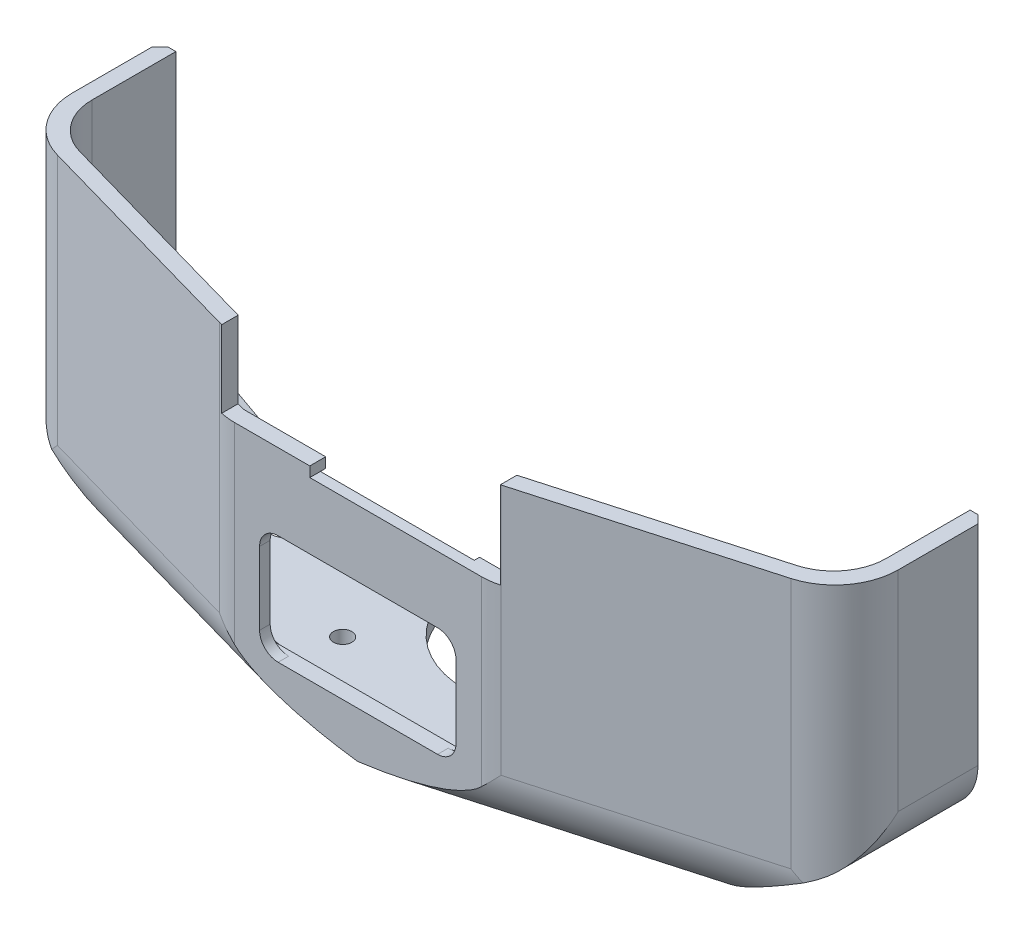
SolidWorks part; units mm, degrees
material "ABS"
ref_plane "Front Plane" through (0, 0, 0) normal (0, 0, 1) x (1, 0, 0)
ref_plane "Top Plane" through (0, 0, 0) normal (0, 1, 0) x (1, 0, 0)
ref_plane "Right Plane" through (0, 0, 0) normal (1, 0, 0) x (0, 0, -1)
sketch "Sketch1" plane through (0, 0, 0) normal (0, 0, 1) x (1, 0, 0)
  line L0 (-78, -21.6306) -> (78, -21.6306) construction
  line L1 (-52, -41.6306) -> (52, -41.6306)
  line L2 (-78, -27.6306) -> (-78, 17.8694)
  line L3 (-78, 17.8694) -> (78, 17.8694)
  line L4 (78, -27.6306) -> (78, 17.8694)
  line L5 (-78, -27.6306) -> (-52, -41.6306)
  line L7 (78, -27.6306) -> (52, -41.6306)
  line L8 (0, -21.6306) -> (0, 0) construction
  line L9 (0, -41.6306) -> (0, -21.6306) construction
  dimension "D1" = 39.5
  dimension "D2" = 156
  dimension "D3" = 14
  dimension "D5" = 104
  dimension "D6" = 20
extrude "Boss-Extrude1" add sketch "Sketch1" along normal blind 30 and the other way blind 10.64
sketch "Sketch2" plane through (0, 17.8694, 0) normal (0, 1, 0) x (1, 0, 0)
  line L0 (-78, -15) -> (-25, -30)
  line L1 (-78, -30) -> (-78, 10.64) construction
  line L2 (78, -30) -> (-78, -30) construction
  line L3 (-25, -30) -> (25, -30)
  line L4 (25, -30) -> (78, -15)
  line L5 (78, -30) -> (78, 10.64) construction
  line L6 (78, -15) -> (78, -44.6495)
  line L7 (78, -44.6495) -> (-78, -44.6495)
  line L8 (-78, -44.6495) -> (-78, -15)
  dimension "D1" = 50
  dimension "D2" = 15
extrude "Cut-Extrude1" cut sketch "Sketch2" against normal through all
shell "Shell1" thickness 3
sketch "Sketch7" plane through (0, 14.8694, 0) normal (0, -1, 0) x (1, 0, 0)
  line L0 (-52, -10.64) -> (52, -10.64) construction
  line L3 (-24.34, 27.069) -> (24.34, 27.069)
  line L6 (75, -10.64) -> (-75, -10.64)
  line L10 (75, -10.64) -> (75, 5.1686)
  line L13 (24.34, 27.069) -> (67.7232, 14.7907)
  line L14 (-24.34, 27.069) -> (-67.7232, 14.7907)
  line L15 (-75, -10.64) -> (-75, 5.1686)
  line L16 (78, -10.64) -> (78, 15) construction
  line L17 (-78, -10.64) -> (-78, 15) construction
  line L19 (-25, 30) -> (-78, 15) construction
  line L20 (78, 15) -> (25, 30) construction
  line L21 (65, 5.1686) -> (-65, 5.1686) construction
  arc A0 (75, 5.1686) -> (67.7232, 14.7907) centre (65, 5.1686) ccw
  arc A1 (-67.7232, 14.7907) -> (-75, 5.1686) centre (-65, 5.1686) ccw
  dimension "D1" = 3
  dimension "D2" = 3
  dimension "D3" = 3
  dimension "D4" = 10
  dimension "D5" = 10
  dimension "D6" = 48.68
  dimension "D7" = 0.66
extrude "Cut-Extrude4" cut sketch "Sketch7" against normal blind 10 and the other way blind 4
fillet "Fillet1" radius 12 12 edges at (0, -41.6306, 30) (-65, -34.6306, 18.6792) (65, -34.6306, 18.6792) (-78, -4.8806, 15) (-38.5, -41.6306, 26.1792) (-25, -11.8806, 30) (38.5, -41.6306, 26.1792) (25, -11.8806, 30) (78, -4.8806, 15) (-37.9136, -38.6306, 23.2274) (37.9136, -38.6306, 23.2274) (0, -38.6306, 27)
sketch "Sketch4" plane through (0, -38.6306, 0) normal (0, 1, 0) x (1, 0, 0)
  line L0 (-42.696, -12.86) -> (63.1659, -12.86) construction
  line L1 (0, 63.5417) -> (0, -42.2617) construction
  line L4 (-51.2436, 10.64) -> (51.2436, 10.64) construction
  circle A0 centre (-20, -12.86) radius 1.75
  circle A1 centre (20, -12.86) radius 1.75
  point P12 (0, 10.64)
  dimension "D1" = 3.5
  dimension "D2" = 3.5
  dimension "D3" = 20
  dimension "D4" = 20
  dimension "D5" = 23.5
extrude "Cut-Extrude2" cut sketch "Sketch4" against normal blind 30
sketch "Sketch18" plane through (0, 14.8694, 0) normal (0, -1, 0) x (1, 0, 0)
  line L0 (75, 5.1686) -> (75, 12.7312) construction
  line L1 (75, 12.7312) -> (67.7232, 14.7907) construction
  line L2 (-67.7232, 14.7907) -> (-75, 12.7312) construction
  line L3 (-75, 12.7312) -> (-75, 5.1686) construction
  line L4 (75, 5.1686) -> (75, 12.7312)
  line L5 (75, 12.7312) -> (67.7232, 14.7907)
  line L6 (-67.7232, 14.7907) -> (-75, 12.7312)
  line L7 (-75, 12.7312) -> (-75, 5.1686)
  arc A0 (75, 5.1686) -> (67.7232, 14.7907) centre (65, 5.1686) ccw construction
  arc A1 (-67.7232, 14.7907) -> (-75, 5.1686) centre (-65, 5.1686) ccw construction
  arc A2 (75, 5.1686) -> (67.7232, 14.7907) centre (65, 5.1686) ccw
  arc A3 (-67.7232, 14.7907) -> (-75, 5.1686) centre (-65, 5.1686) ccw
extrude "Boss-Extrude2" add sketch "Sketch18" along normal up to next
fillet "Fillet2" radius 10 4 edges at (-78, -27.6306, -2.3576) (-52, -41.6306, -0.3764) (52, -41.6306, -0.3764) (78, -27.6306, -2.3576)
sketch "Sketch12" plane through (0, -41.6306, 0) normal (0, -1, 0) x (1, 0, 0)
  line L1 (17.1361, -11.1904) -> (-17.1361, -11.1904)
  line L3 (-49.4788, -10.64) -> (49.4788, -10.64) construction
  arc A0 (17.1361, -11.1904) -> (-17.1361, -11.1904) centre (0, -7.64) ccw
  dimension "D1" = 35
  dimension "D2" = 3
extrude "Cut-Extrude5" cut sketch "Sketch12" against normal up to surface (3 mm away) up to face at (-20, -38.6306, 14.61)
sketch "Sketch13" plane through (0, 0, 30) normal (0, 0, 1) x (1, 0, 0)
  line L0 (23.3346, 17.8694) -> (-23.3346, 17.8694) construction
  line L2 (26.5, 17.8694) -> (26.5, 1.4694)
  line L5 (0, -40.4493) -> (0, 17.8694) construction
  line L13 (-26, 17.8694) -> (-26, 3.3737)
  line L14 (26.5, 1.4694) -> (-9.07, 1.4694)
  line L15 (26.5, 17.8694) -> (0, 17.8694)
  line L16 (0, 17.8694) -> (-26, 17.8694)
  line L17 (-26, 3.3737) -> (-9.07, 3.3737)
  line L18 (-9.07, 17.8694) -> (-9.07, 1.4694) construction
  line L19 (-9.07, 3.3737) -> (-9.07, 1.4694)
  dimension "D1" = 26
  dimension "D2" = 16.4
  dimension "D7" = 26.5
extrude "Cut-Extrude6" cut sketch "Sketch13" against normal blind 10
sketch "Sketch16" plane through (0, 0, 30) normal (0, 0, 1) x (1, 0, 0)
  line L0 (-9.07, 1.4694) -> (23.3346, 1.4694) construction
  line L1 (18.55, -31.7306) -> (-18.55, -31.7306)
  line L2 (18.55, -31.7306) -> (18.55, -11.0306)
  line L3 (18.55, -11.0306) -> (-18.55, -11.0306)
  line L4 (-18.55, -31.7306) -> (-18.55, -11.0306)
  line L5 (0, 1.4694) -> (0, -31.7306) construction
  dimension "D1" = 12.5
  dimension "D2" = 20.7
  dimension "D3" = 37.1
extrude "Cut-Extrude8" cut sketch "Sketch16" against normal up to surface (3 mm away)
fillet "Fillet3" radius 3.48 4 edges at (-18.55, -11.0306, 28.5) (-18.55, -31.7306, 28.5) (18.55, -31.7306, 28.5) (18.55, -11.0306, 28.5)
sketch "Sketch17" plane through (0, -31.7306, 0) normal (0, 1, 0) x (1, 0, 0)
  line L1 (-9.07, -27) -> (24.5836, -27) construction
  line L2 (-20, -27) -> (20, -27)
  line L3 (-20, -27) -> (-20, -28)
  line L4 (-20, -28) -> (20, -28)
  line L5 (20, -27) -> (20, -28)
  line L6 (-9.07, -30) -> (23.3346, -30) construction
  point P9 (0, -27)
  dimension "D1" = 2
  dimension "D2" = 40
extrude "Cut-Extrude10" cut sketch "Sketch17" along normal up to surface (33.2 mm away) up to face at (13.7987, 1.4694, 28.3564)
sketch "Sketch19" plane through (0, 17.8694, 0) normal (0, 1, 0) x (1, 0, 0)
  line L1 (-75, 10.64) -> (-76.6, 10.64)
  line L2 (-75, 10.64) -> (-75, -3.86)
  line L3 (-75, -3.86) -> (-76.6, -3.86)
  line L4 (-76.6, 10.64) -> (-76.6, -3.86)
  line L5 (75, 10.64) -> (76.6, 10.64)
  line L6 (75, 10.64) -> (75, -3.86)
  line L7 (75, -3.86) -> (76.6, -3.86)
  line L8 (76.6, 10.64) -> (76.6, -3.86)
  dimension "D1" = 14.5
  dimension "D2" = 1.6
extrude "Cut-Extrude11" [suppressed] cut sketch "Sketch19" against normal blind 12
sketch "Sketch20" plane through (78, 0, 0) normal (1, 0, 0) x (0, 0, -1)
  line L0 (10.64, 17.8694) -> (-5.9249, 17.8694) construction
  line L1 (10.64, -21.6577) -> (10.64, 17.8694) construction
  circle A0 centre (1.64, 12.3694) radius 1.75
  dimension "D1" = 3.5
  dimension "D2" = 5.5
  dimension "D3" = 9
extrude "Cut-Extrude12" [suppressed] cut sketch "Sketch20" against normal through all
sketch "Sketch21" plane through (0, -38.6306, 0) normal (0, 1, 0) x (1, 0, 0)
  line L0 (-52.8475, 10.64) -> (-52.8475, -8.7796)
  line L1 (-75, 10.64) -> (-51.2436, 10.64) construction
  line L2 (-52.8475, -8.7796) -> (-33.4259, -22.2861)
  line L3 (-33.4259, -22.2861) -> (33.4259, -22.2861)
  line L4 (33.4259, -22.2861) -> (52.8475, -7.1244)
  line L5 (52.8475, -7.1244) -> (52.8475, 10.64)
  line L6 (51.2436, 10.64) -> (75, 10.64) construction
  line L7 (-52.8475, 10.64) -> (52.8475, 10.64)
  point P20 (0, 10.64)
  point P22 (0, -22.2861)
extrude "Cut-Extrude13" cut sketch "Sketch21" along normal blind 10
sketch "Sketch22" plane through (0, -41.6306, 0) normal (0, -1, 0) x (1, 0, 0)
  line L0 (-43.75, -0.64) -> (43.75, -0.64) construction
  line L1 (-49.4788, -10.64) -> (-17.2409, -10.64) construction
  line L2 (-47.25, -0.64) -> (-47.25, -10.64)
  line L3 (-47.25, -10.64) -> (-40.25, -10.64)
  line L4 (-40.25, -10.64) -> (-40.25, -0.64)
  line L5 (40.25, -0.64) -> (40.25, -10.64)
  line L6 (17.2409, -10.64) -> (49.4788, -10.64) construction
  line L7 (40.25, -10.64) -> (47.25, -10.64)
  line L8 (47.25, -10.64) -> (47.25, -0.64)
  circle A0 centre (-43.75, -0.64) radius 3.5
  circle A1 centre (43.75, -0.64) radius 3.5
  dimension "D1" = 7
  dimension "D2" = 87.5
  dimension "D3" = 10
  dimension "D4" = 43.75
extrude "Cut-Extrude14" cut sketch "Sketch22" against normal blind 10
chamfer "Chamfer1" distance 1.5 angle 45 12 edges at (-63.4804, -35.4489, -10.64) (78, -1.8942, -10.64) (63.4804, -35.4489, -10.64) (-48.3644, -41.6306, -10.64) (76.5852, -26.7856, -10.64) (51.9235, -41.3272, -10.64) (-51.9235, -41.3272, -10.64) (-76.5852, -26.7856, -10.64) (28.7455, -41.6306, -10.64) (-78, -1.8942, -10.64) (48.3644, -41.6306, -10.64) (-28.7455, -41.6306, -10.64)
sketch "Sketch23" plane through (0, 0, 28) normal (0, 0, -1) x (-1, 0, 0)
  line L0 (-15.05, -11.0306) -> (15.07, -11.0306) construction
  line L1 (-22.6973, -5.3163) -> (21.4218, -5.3163)
  line L2 (-22.6973, -5.3163) -> (-22.6973, -9.5306)
  line L3 (-22.6973, -9.5306) -> (21.4218, -9.5306)
  line L4 (21.4218, -5.3163) -> (21.4218, -9.5306)
  dimension "D1" = 1.5
extrude "Boss-Extrude3" add sketch "Sketch23" along normal blind 3
chamfer "Chamfer2" distance 2 angle 60 1 edges at (0, -9.5306, 28)
equation "\"D4@Sketch22\"=87.5/2"
